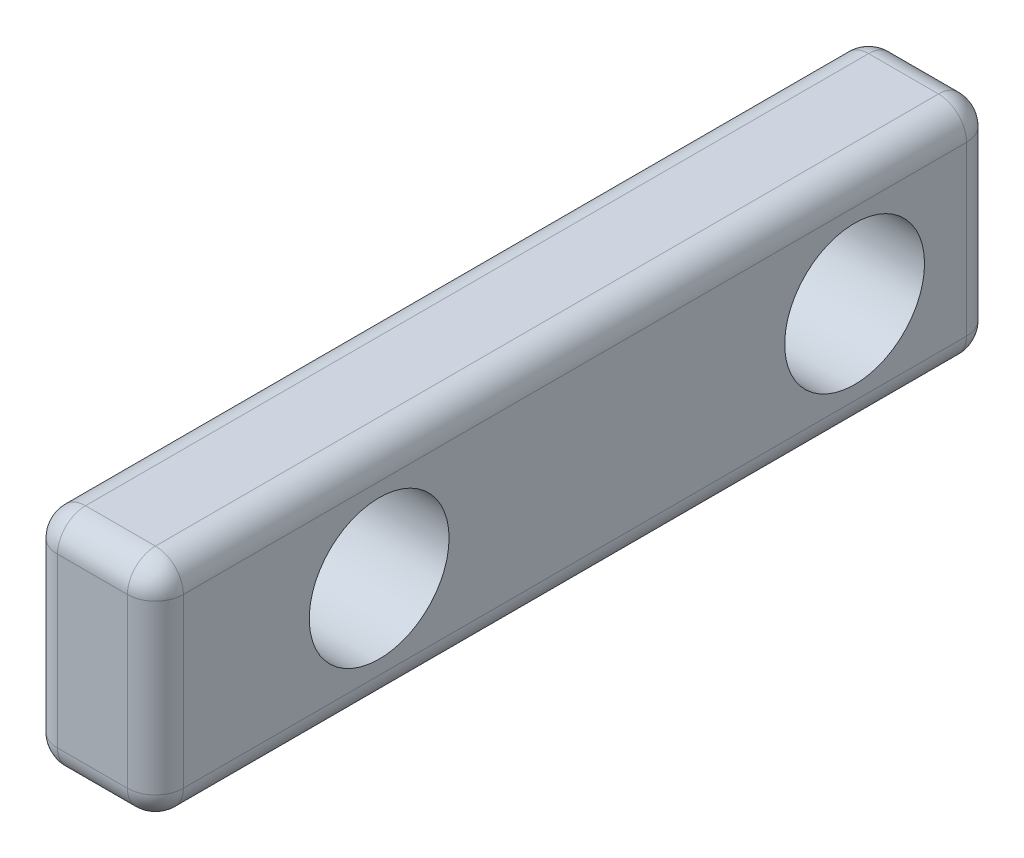
SolidWorks part; units mm, degrees
material "ABS"
ref_plane "前视基准面" through (0, 0, 0) normal (0, 0, 1) x (1, 0, 0)
ref_plane "上视基准面" through (0, 0, 0) normal (0, 1, 0) x (1, 0, 0)
ref_plane "右视基准面" through (0, 0, 0) normal (1, 0, 0) x (0, 0, -1)
other "Configuration Table"
sketch "草图1" plane through (0, 0, 0) normal (0, 0, 1) x (1, 0, 0)
  line L1 (0, 8) -> (4.5, 8)
  line L2 (0, 8) -> (0, 0)
  line L3 (0, 0) -> (4.5, 0)
  line L4 (4.5, 8) -> (4.5, 0)
  dimension "D1" = 4.5
  dimension "D2" = 8
extrude "凸台-拉伸1" add sketch "草图1" along normal blind 30
sketch "草图4" plane through (4.5, 0, 0) normal (1, 0, 0) x (0, 0, -1)
  line L0 (-30, 4) -> (0, 4) construction
  line L1 (-30, 0) -> (-30, 8) construction
  line L2 (0, 0) -> (0, 8) construction
  circle A0 centre (-5, 4) radius 2.5
  circle A1 centre (-22, 4) radius 2.5
  dimension "D1" = 5
  dimension "D3" = 17
  dimension "D2" = 5
extrude "切除-拉伸2" cut sketch "草图4" against normal through all
sketch "草图7" plane through (0, 0, 0) normal (-1, 0, 0) x (0, 0, 1)
  circle A0 centre (5, 4) radius 3.5
  circle A1 centre (22, 4) radius 3.5
  dimension "D1" = 7
extrude "切除-拉伸4" cut sketch "草图7" against normal blind 0.5
fillet "圆角1" radius 1 12 edges at (0, 0, 15) (4.5, 0, 15) (4.5, 4, 30) (2.25, 0, 30) (0, 4, 30) (4.5, 8, 15) (2.25, 8, 30) (0, 8, 15) (2.25, 0, 0) (4.5, 4, 0) (2.25, 8, 0) (0, 4, 0)
